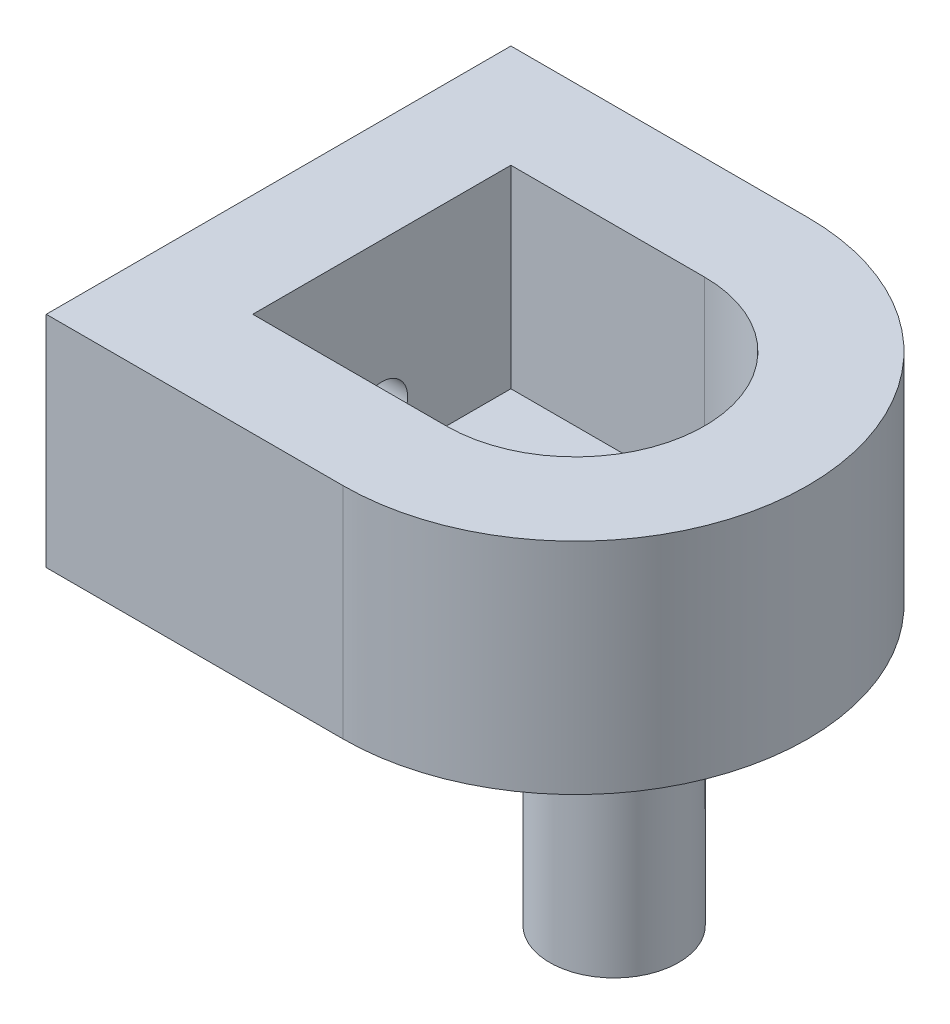
SolidWorks part; units mm, degrees
ref_plane "Front Plane" through (0, 0, 0) normal (0, 0, 1) x (1, 0, 0)
ref_plane "Top Plane" through (0, 0, 0) normal (0, 1, 0) x (1, 0, 0)
ref_plane "Right Plane" through (0, 0, 0) normal (1, 0, 0) x (0, 0, -1)
sketch "Sketch1" plane through (0, 0, 0) normal (0, 1, 0) x (1, 0, 0)
  line L0 (-23, 18) -> (0, 18)
  line L1 (-15, 10) -> (0, 10)
  line L2 (-15, 10) -> (-15, -10)
  line L3 (-15, -10) -> (0, -10)
  line L4 (0, 10) -> (0, -10) construction
  line L7 (-23, -18) -> (0, -18)
  line L8 (-23, 18) -> (-23, -18)
  arc A0 (0, 10) -> (0, -10) centre (0, 0) cw
  arc A1 (0, 18) -> (0, -18) centre (0, 0) cw
  point P0 (0, 0)
  point P12 (0, 0)
  point P13 (0, 0)
  dimension "D1" = 15
  dimension "D2" = 20
  dimension "D3" = 8
extrude "Boss-Extrude1" add sketch "Sketch1" along normal blind 15
extrude "Boss-Extrude2" add sketch "Sketch1<2>" against normal blind 2 contours A1 L7 L8 L0
sketch "Sketch1<2>" plane through (0, 0, 0) normal (0, 1, 0) x (1, 0, 0) same geometry as "Sketch1"
sketch "Sketch2" plane through (0, -2, 0) normal (0, -1, 0) x (-1, 0, 0)
  circle A0 centre (-3, 0) radius 5
  circle A1 centre (-3, 0) radius 3
  point P4 (0, 0)
  point P5 (0, 0)
  point P6 (-5.1187, 0)
  dimension "D1" = 10
  dimension "D2" = 6
  dimension "D3" = 3
extrude "Boss-Extrude3" add sketch "Sketch2" along normal blind 20 contours A1 | A0 A1 region at (7.8586, -2, 0) region at (3, -2, 0)
extrude "Cut-Extrude1" cut sketch "Sketch2<3>" against normal through all and the other way offset from surface 2 contours A1 other way up to face at (3, -22, -5)
sketch "Sketch2<3>" plane through (0, -2, 0) normal (0, -1, 0) x (-1, 0, 0) same geometry as "Sketch2"
sketch "Sketch3" plane through (-23, 0, 0) normal (-1, 0, 0) x (0, 0, 1)
  line L0 (-18, -2) -> (18, -2) construction
  circle A0 centre (0, 3.47) radius 2
  dimension "D1" = 4
  dimension "D2" = 5.47
extrude "Cut-Extrude2" cut sketch "Sketch3" against normal blind 20
ref_plane "Plane1" through (0, -2, 0) normal (0, -1, 0) x (-1, 0, 0)
split "Split1" trim tools "Plane1" bodies to split 105 resulting bodies 106 107
